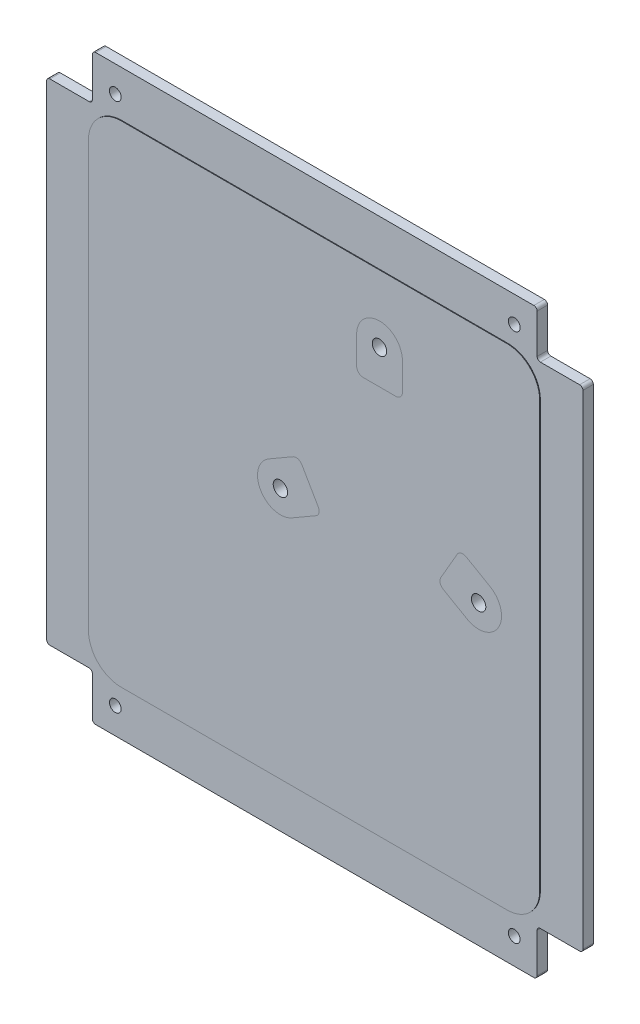
SolidWorks part; units mm, degrees
material "PET"
ref_plane "Front Plane" through (0, 0, 0) normal (0, 0, 1) x (1, 0, 0)
ref_plane "Top Plane" through (0, 0, 0) normal (0, 1, 0) x (1, 0, 0)
ref_plane "Right Plane" through (0, 0, 0) normal (1, 0, 0) x (0, 0, -1)
sketch "Sketch1" plane through (0, 0, 0) normal (0, 0, 1) x (1, 0, 0)
  line L0 (-34, 44) -> (-34, 38)
  line L1 (-33.5, -44.5) -> (33.5, -44.5)
  line L2 (-41, 37) -> (-41, -37)
  line L3 (-33.5, 44.5) -> (33.5, 44.5)
  line L4 (41, -37) -> (41, 37)
  line L5 (34, -44) -> (34, -38)
  line L6 (34.5, -37.5) -> (40.5, -37.5)
  line L7 (-34.5, 37.5) -> (-40.5, 37.5)
  line L8 (34, 44) -> (34, 38)
  line L9 (34.5, 37.5) -> (40.5, 37.5)
  line L10 (-40.5, -37.5) -> (-34.5, -37.5)
  line L11 (-34, -38) -> (-34, -44)
  line L12 (-34.5, -38) -> (34.5, 38) construction
  line L13 (34.5, -38) -> (-34.5, 38) construction
  arc A0 (-33.5, 44.5) -> (-34, 44) centre (-33.5, 44) ccw
  arc A1 (33.5, 44.5) -> (34, 44) centre (33.5, 44) cw
  arc A2 (34, 38) -> (34.5, 37.5) centre (34.5, 38) ccw
  arc A3 (40.5, 37.5) -> (41, 37) centre (40.5, 37) cw
  arc A4 (33.5, -44.5) -> (34, -44) centre (33.5, -44) ccw
  arc A5 (34.5, -37.5) -> (34, -38) centre (34.5, -38) ccw
  arc A6 (40.5, -37.5) -> (41, -37) centre (40.5, -37) ccw
  arc A7 (-34, -44) -> (-33.5, -44.5) centre (-33.5, -44) ccw
  arc A8 (-34, -38) -> (-34.5, -37.5) centre (-34.5, -38) ccw
  arc A9 (-41, -37) -> (-40.5, -37.5) centre (-40.5, -37) ccw
  arc A10 (-40.5, 37.5) -> (-41, 37) centre (-40.5, 37) ccw
  arc A11 (-34.5, 37.5) -> (-34, 38) centre (-34.5, 38) ccw
  point P0 (0, 0)
  dimension "D4" = 0.5
  dimension "D1" = 7
  dimension "D2" = 7
  dimension "D3" = 7
  dimension "D5" = 7
  dimension "D6" = 7
  dimension "D7" = 7
  dimension "D8" = 7
  dimension "D9" = 7
  dimension "D10" = 89
  dimension "D11" = 82
extrude "Boss-Extrude1" add sketch "Sketch1" along normal blind 1.6
sketch "Esboço1" plane through (0, 0, 1.6) normal (0, 0, 1) x (1, 0, 0)
  line L1 (-29.5, -37.5) -> (29.5, -37.5)
  line L2 (-34.5, -32.5) -> (-34.5, 32.5)
  line L3 (-29.5, 37.5) -> (29.5, 37.5)
  line L4 (34.5, -32.5) -> (34.5, 32.5)
  line L5 (-29.5, -32.5) -> (29.5, 32.5) construction
  line L6 (-29.5, 32.5) -> (29.5, -32.5) construction
  arc A0 (-34.5, 32.5) -> (-29.5, 37.5) centre (-29.5, 32.5) cw
  arc A1 (29.5, 37.5) -> (34.5, 32.5) centre (29.5, 32.5) cw
  arc A2 (34.5, -32.5) -> (29.5, -37.5) centre (29.5, -32.5) cw
  arc A3 (-29.5, -37.5) -> (-34.5, -32.5) centre (-29.5, -32.5) cw
  point P0 (0, 0)
  dimension "D1" = 5
  dimension "D2" = 69
  dimension "D3" = 75
extrude "Boss-Extrude2" add sketch "Esboço1" along normal blind 0.1
hole_wizard "M1.6 Hole1-FixingStructure" positions "Sketch3" profile "Sketch2" hole size "M1.6" standard "DIN"
sketch "Sketch3" plane through (0, 0, 0) normal (0, 0, -1) x (-1, 0, 0)
  line L0 (-33.5, 44.5) -> (33.5, 44.5) construction
  line L1 (33.5, -44.5) -> (-33.5, -44.5) construction
  line L2 (-41, -37) -> (-41, 37) construction
  line L3 (41, 37) -> (41, -37) construction
  point P0 (-30.5, 40.5)
  point P2 (30.5, 40.5)
  point P4 (-30.5, -40.5)
  point P6 (30.5, -40.5)
  dimension "D1" = 4
  dimension "D2" = 4
  dimension "D3" = 10.5
  dimension "D4" = 10.5
sketch "Sketch2" plane through (30.5, 40.5, 0) normal (1, 0, 0) x (0, 1, 0)
  line L0 (0, 0) -> (0, 200.5408)
  line L1 (0, 200.5408) -> (0.9, 200)
  line L2 (0.9, 200) -> (0.9, 0)
  line L5 (0.9, 0) -> (0, 0)
  line L10 (0, 200.5408) -> (-0.9, 200) construction
  line L11 (0, -6.35) -> (0, 107.95) construction
  dimension "Hole Dia." = 1.8
  dimension "Hole Depth" = 200
  dimension "Drill Angle" = 118
sketch "Sketch4" plane through (0, 0, 1.7) normal (0, 0, 1) x (1, 0, 0)
  circle A0 centre (25.1554, 1) radius 1.1 construction
  circle A1 centre (10, 27.25) radius 1.1 construction
  circle A2 centre (-5.1554, 1) radius 1.1 construction
  circle A3 centre (25.1554, 1) radius 1.1
  circle A4 centre (10, 27.25) radius 1.1
  circle A5 centre (-5.1554, 1) radius 1.1
extrude "Cut-Extrude1" cut sketch "Sketch4" against normal up to surface (1.7 mm away) up to face at (29.6, 40.5, 0)
sketch "Sketch5" plane through (0, 0, 1.7) normal (0, 0, 1) x (1, 0, 0)
  line L0 (19.3731, 1.4517) -> (21.8731, 5.7818)
  line L1 (19.3731, 1.4517) -> (21.8731, 5.7818) construction
  line L2 (-1.8731, 5.7818) -> (0.6269, 1.4517)
  line L3 (20.2391, 0.9517) -> (22.7391, 5.2818) construction
  line L4 (-6.9054, 4.0311) -> (-3.2391, 6.1478)
  line L5 (23.4054, -2.0311) -> (20.1795, -0.1686)
  line L6 (23.6795, 5.8936) -> (26.9054, 4.0311)
  line L7 (23.4054, -2.0311) -> (19.7391, 0.0857)
  line L8 (23.2391, 6.1478) -> (26.9054, 4.0311)
  line L9 (0.2609, 0.0857) -> (-3.4054, -2.0311)
  line L10 (-2.7391, 5.2818) -> (-0.2391, 0.9517) construction
  line L11 (12.5, 22.0165) -> (7.5, 22.0165)
  line L12 (13.5, 27.25) -> (13.5, 23.0165)
  line L13 (6.5, 23.0165) -> (6.5, 27.25)
  line L14 (12.5, 23.0165) -> (7.5, 23.0165) construction
  circle A0 centre (10, 9.75) radius 10 construction
  arc A1 (19.7391, 0.0857) -> (19.3731, 1.4517) centre (20.2391, 0.9517) cw
  arc A2 (21.8731, 5.7818) -> (23.2391, 6.1478) centre (22.7391, 5.2818) cw
  arc A3 (-3.2391, 6.1478) -> (-1.8731, 5.7818) centre (-2.7391, 5.2818) cw
  arc A4 (0.6269, 1.4517) -> (0.2609, 0.0857) centre (-0.2391, 0.9517) cw
  arc A5 (23.4054, -2.0311) -> (26.9054, 4.0311) centre (25.1554, 1) ccw
  arc A6 (23.4054, -2.0311) -> (26.9054, 4.0311) centre (25.1554, 1) ccw
  arc A7 (-6.9054, 4.0311) -> (-3.4054, -2.0311) centre (-5.1554, 1) ccw
  arc A8 (13.5, 23.0165) -> (12.5, 22.0165) centre (12.5, 23.0165) cw
  arc A9 (7.5, 22.0165) -> (6.5, 23.0165) centre (7.5, 23.0165) cw
  arc A10 (13.5, 27.25) -> (6.5, 27.25) centre (10, 27.25) ccw
  point P0 (10, 9.75)
  point P45 (10, 9.75)
  dimension "D3" = 1
  dimension "D1" = 1
  dimension "D2" = 1
  dimension "D4" = 3
split line "Split Line1"
